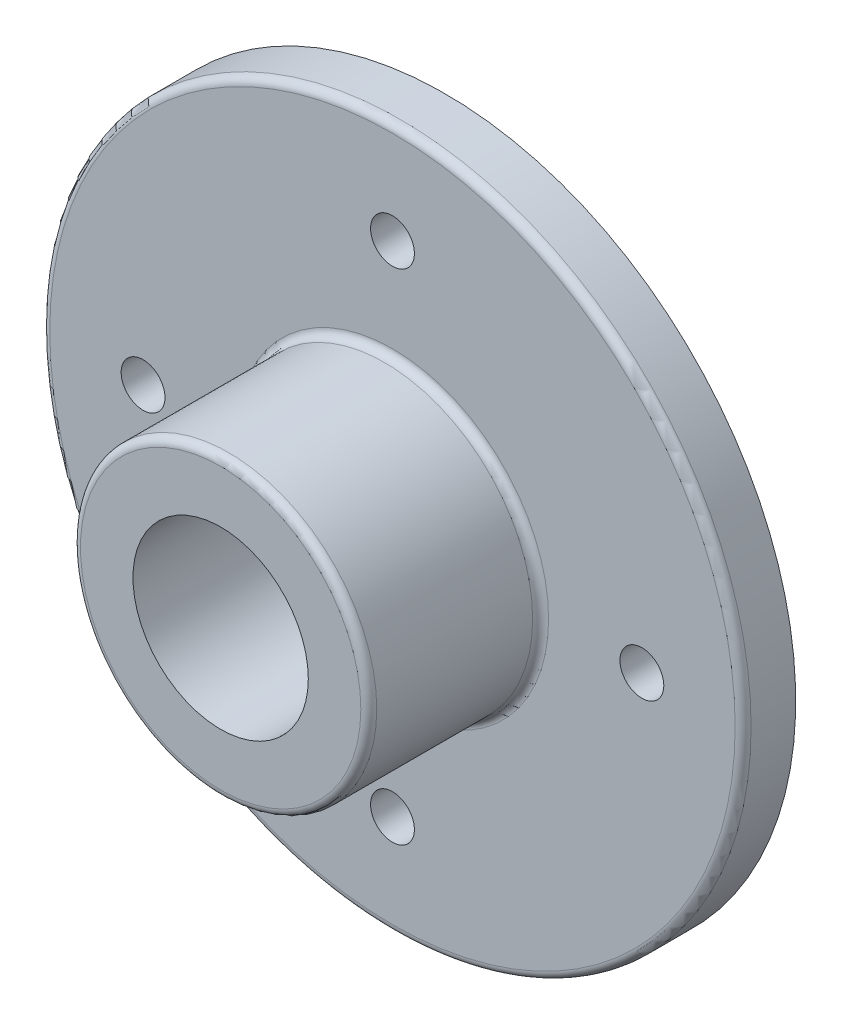
SolidWorks part; units mm, degrees
material "PVC Rigid"
ref_plane "Front Plane" through (0, 0, 0) normal (0, 0, 1) x (1, 0, 0)
ref_plane "Top Plane" through (0, 0, 0) normal (0, 1, 0) x (1, 0, 0)
ref_plane "Right Plane" through (0, 0, 0) normal (1, 0, 0) x (0, 0, -1)
sketch "Sketch0" plane through (0, 0, 0) normal (1, 0, 0) x (0, 0, -1)
  line L0 (0, 0) -> (-32.512, 0) construction
  point P3 (-14.732, 0)
  point P4 (-4.064, 0)
  dimension "Q" = 14.732
  dimension "C" = 32.512
  dimension "N" = 4.064
sketch "Sketch1" plane through (0, 0, 0) normal (0, 0, 1) x (1, 0, 0)
  circle A0 centre (0, 0) radius 50.8
  circle A1 centre (0, 0) radius 16.8275 construction
  circle A2 centre (0, 0) radius 39.243 construction
  circle A3 centre (0, 39.243) radius 7.9375 construction
  circle A4 centre (0, 0) radius 21.463 construction
  circle A5 centre (0, 0) radius 12.1539 construction
  circle A6 centre (0, 0) radius 16.637 construction
  point P9 (0, 16.8275)
  point P10 (0, 16.637)
  point P11 (0, 12.1539)
  dimension "B" = 78.486
  dimension "Bolt Hole Size" = 15.875
  dimension "Pipe OD A" = 33.655
  dimension "Hub OD" = 42.926
  dimension "Pipe ID" = 24.3078
  dimension "Pipe OD B" = 33.274
extrude "Extrude1" add sketch "Sketch1" along normal blind 7.62
sketch "Sketch2" plane through (0, 0, 7.62) normal (0, 0, 1) x (1, 0, 0)
  circle A0 centre (0, 0) radius 21.463 construction
  circle A1 centre (0, 0) radius 21.463
extrude "Extrude2" add sketch "Sketch2" along normal up to vertex (24.892 mm away) up to point (0, 0, 32.512)
sketch "Sketch3" plane through (0, 0, 7.62) normal (0, 0, 1) x (1, 0, 0)
  line L0 (0, 21.463) -> (0, 50.8) construction
  line L1 (0, 21.463) -> (0, 0) construction
  circle A1 centre (0, 36.1315) radius 3.175
extrude "Extrude3" cut sketch "Sketch3" against normal through all
ref_axis "Axis1" through (0, 0, -1.6256) along (0, 0, 1)
pattern_circular "CirPattern1" count 4 over 360 about axis through (0, 0, -1.6256) along (0, 0, 1) of "Extrude3"
fillet "Fillet1" radius 1.1545 3 edges at (21.463, 0, 32.512) (21.463, 0, 7.62) (50.8, 0, 7.62) tangent propagation no
sketch "Sketch4" plane through (0, 0, 63.5) normal (1, 0, 0) x (0, 0, -1)
  line L0 (-0.001, 0) -> (-0.001, 12.7)
  line L1 (-0.001, 12.7) -> (79.0164, 12.7)
  line L2 (79.0164, 12.7) -> (79.0164, 0)
  line L3 (79.0164, 0) -> (-0.001, 0)
revolve "Cut-Revolve1" cut sketch "Sketch4" angle 360 about L3
